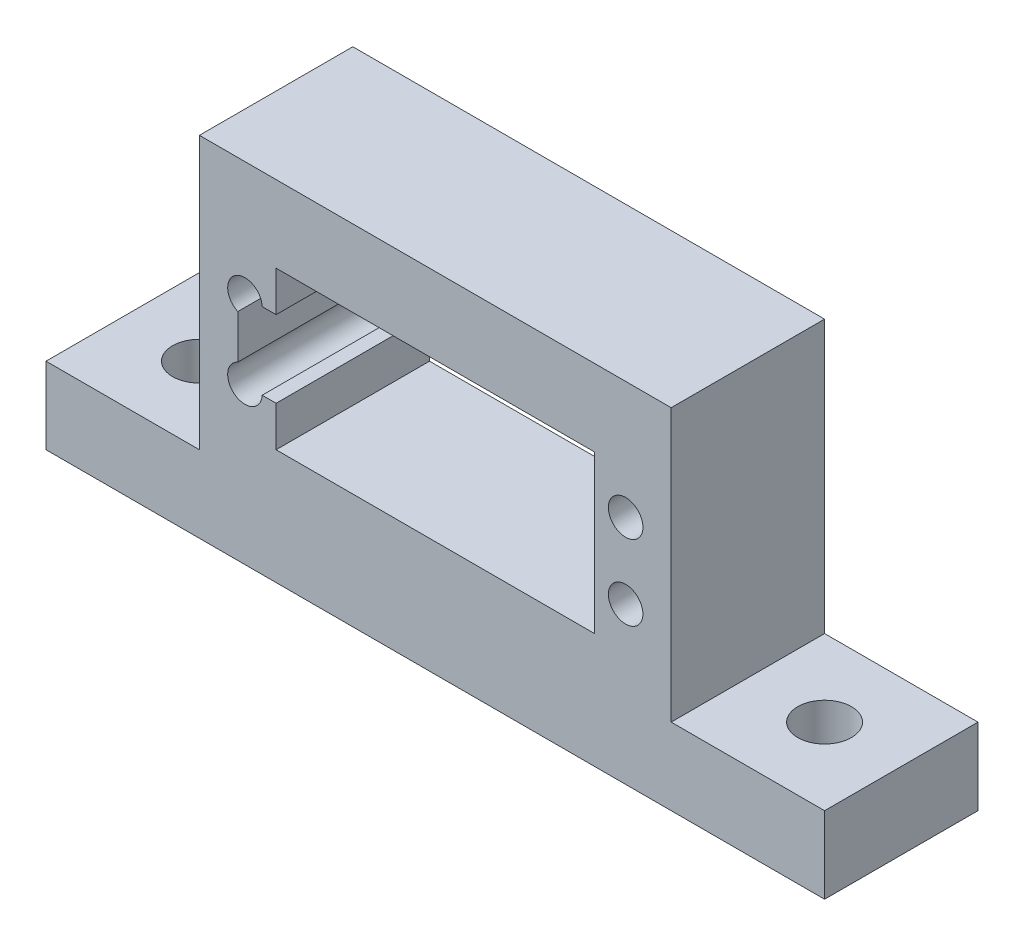
SolidWorks part; units mm, degrees
ref_plane "Front Plane" through (0, 0, 0) normal (0, 0, 1) x (1, 0, 0)
ref_plane "Top Plane" through (0, 0, 0) normal (0, 1, 0) x (1, 0, 0)
ref_plane "Right Plane" through (0, 0, 0) normal (1, 0, 0) x (0, 0, -1)
sketch "Sketch1" plane through (0, 0, 0) normal (0, 0, 1) x (1, 0, 0)
  line L0 (-50.75, 0) -> (50.75, 0)
  line L1 (50.75, 0) -> (50.75, 10)
  line L2 (50.75, 10) -> (30.75, 10)
  line L3 (30.75, 10) -> (30.75, 45.5)
  line L4 (30.75, 45.5) -> (-30.75, 45.5)
  line L5 (0, 0) -> (0, 132.122) construction
  line L6 (-20.75, 35.5) -> (20.75, 35.5)
  line L7 (20.75, 35.5) -> (20.75, 15)
  line L8 (20.75, 15) -> (-20.75, 15)
  line L10 (-30.75, 10) -> (-30.75, 45.5)
  line L11 (-50.75, 10) -> (-30.75, 10)
  line L12 (-50.75, 0) -> (-50.75, 10)
  line L13 (-20.75, 30.25) -> (-22.5672, 30.25)
  line L14 (-25.75, 28.1035) -> (-25.75, 22.3965)
  line L15 (-22.5672, 20.25) -> (-20.75, 20.25)
  line L16 (-20.75, 35.5) -> (-20.75, 30.25)
  line L18 (-20.75, 20.25) -> (-20.75, 15)
  line L19 (27.065, 11.4349) -> (27.065, 38.773) construction
  line L20 (20.75, 25.25) -> (36.6589, 25.25) construction
  circle A0 centre (24.815, 30.15) radius 2.25
  circle A1 centre (24.815, 20.35) radius 2.25
  arc A2 (-25.75, 22.3965) -> (-22.5672, 20.25) centre (-24.815, 20.35) ccw
  arc A3 (-25.75, 28.1035) -> (-22.5672, 30.25) centre (-24.815, 30.15) cw
  point P15 (-25.75, 25.25)
  point P18 (0, 15)
  point P19 (0, 35.5)
  point P20 (0, 45.5)
  dimension "D11" = 4.5
  dimension "D1" = 41.5
  dimension "D2" = 20.5
  dimension "D3" = 15
  dimension "D4" = 10
  dimension "D5" = 20
  dimension "D6" = 10
  dimension "D7" = 10
  dimension "D8" = 10
  dimension "D9" = 5
  dimension "D10" = 54.13
  dimension "D12" = 4.9
  dimension "D13" = 5
extrude "Boss-Extrude1" add sketch "Sketch1" along normal blind 20
sketch "Sketch2" plane through (0, 10, 0) normal (0, 1, 0) x (1, 0, 0)
  line L0 (50.75, -10) -> (-50.75, -10) construction
  line L1 (50.75, -20) -> (50.75, 0) construction
  line L2 (-50.75, -20) -> (-50.75, 0) construction
  line L3 (40.75, 0) -> (40.75, -20) construction
  line L4 (50.75, 0) -> (30.75, 0) construction
  line L5 (50.75, -20) -> (30.75, -20) construction
  line L6 (0, 0) -> (0, -20) construction
  line L7 (30.75, 0) -> (-30.75, 0) construction
  line L8 (30.75, -20) -> (-30.75, -20) construction
  circle A0 centre (40.75, -10) radius 3.5
  circle A1 centre (-40.75, -10) radius 3.5
  point P20 (40.75, -10)
  point P21 (38.5835, -10)
  dimension "D1" = 7
extrude "Cut-Extrude1" cut sketch "Sketch2" against normal through all
